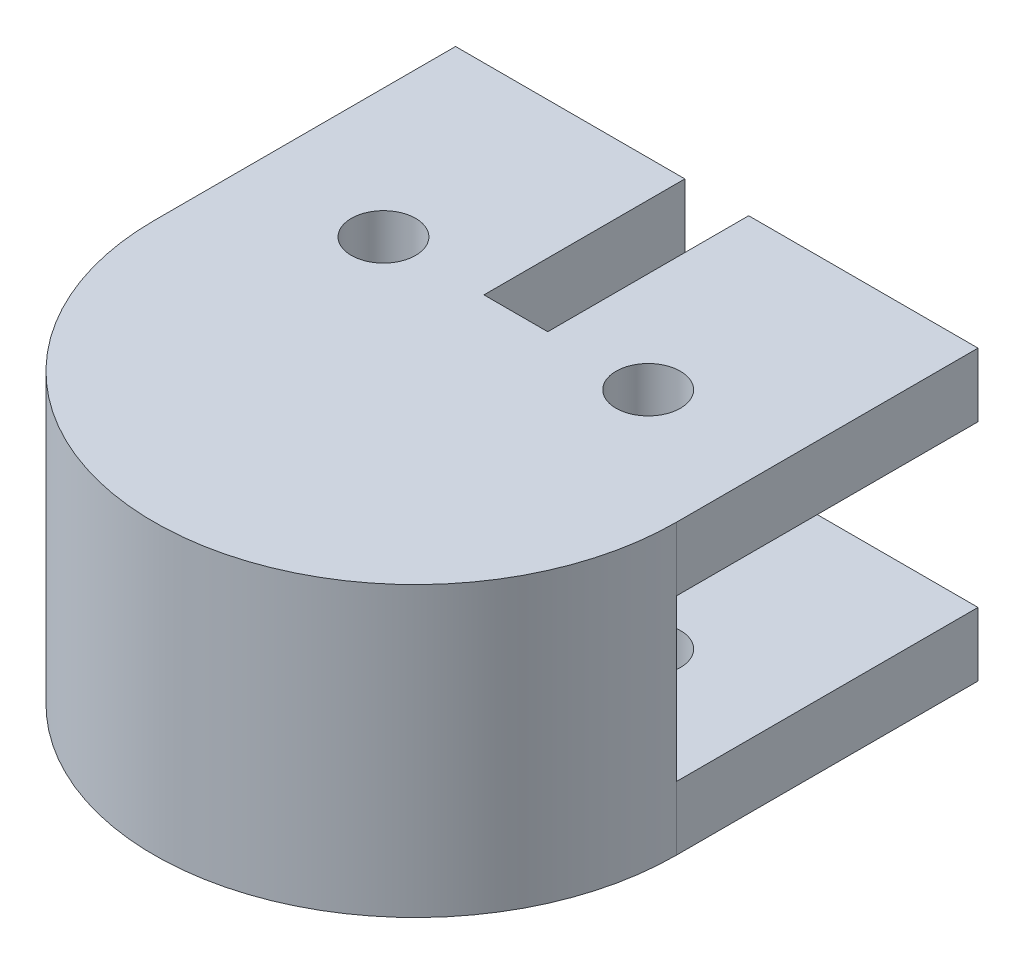
SolidWorks part; units mm, degrees
ref_plane "Front Plane" through (0, 0, 0) normal (0, 0, 1) x (1, 0, 0)
ref_plane "Top Plane" through (0, 0, 0) normal (0, 1, 0) x (1, 0, 0)
ref_plane "Right Plane" through (0, 0, 0) normal (1, 0, 0) x (0, 0, -1)
sketch "Sketch1" plane through (0, 0, 0) normal (0, 1, 0) x (1, 0, 0)
  line L0 (-1.5875, 0) -> (1.5875, 0)
  line L1 (1.5875, 0) -> (1.5875, 10)
  line L2 (1.5875, 10) -> (13, 10)
  line L3 (13, 10) -> (13, -5)
  line L4 (0, 0) -> (0, -18) construction
  line L5 (-13, 10) -> (-13, -5)
  line L6 (-1.5875, 10) -> (-13, 10)
  line L7 (-1.5875, 0) -> (-1.5875, 10)
  arc A0 (-13, -5) -> (13, -5) centre (0, -5) ccw
  circle A1 centre (6.5875, 0) radius 1.6
  circle A2 centre (-6.5875, 0) radius 1.6
  point P10 (0, 0)
  dimension "D5" = 3.2
  dimension "D1" = 1.5875
  dimension "D2" = 11.4125
  dimension "D3" = 15
  dimension "D4" = 10
  dimension "D6" = 5
extrude "Boss-Extrude1" add sketch "Sketch1" along normal blind 3.175
sketch "Sketch3" plane through (0, 0, 0) normal (0, -1, 0) x (1, 0, 0)
  line L0 (4.0875, -10) -> (1.5875, -10)
  line L1 (13, -10) -> (1.5875, -10) construction
  line L2 (1.5875, -10) -> (1.5875, 0)
  line L3 (1.5875, 0) -> (-1.5875, 0)
  line L4 (-1.5875, 0) -> (-1.5875, -10)
  line L5 (-1.5875, -10) -> (-4.0875, -10)
  line L6 (-1.5875, -10) -> (-13, -10) construction
  line L7 (-4.0875, -10) -> (-4.0875, 5)
  line L8 (-4.0875, 5) -> (-13, 5)
  line L9 (4.0875, -10) -> (4.0875, 5)
  line L10 (4.0875, 5) -> (13, 5)
  arc A0 (13, 5) -> (-13, 5) centre (0, 5) ccw
  dimension "D1" = 2.5
extrude "Boss-Extrude3" add sketch "Sketch3" along normal blind 4
ref_plane "Plane2" through (0, -4, 0) normal (0, -1, 0) x (-1, 0, 0)
mirror "Mirror11" about plane through (0, -4, 0) normal (0, -1, 0) of "Boss-Extrude3"
mirror "Mirror12" about plane through (0, -4, 0) normal (0, -1, 0) of "Boss-Extrude1"
